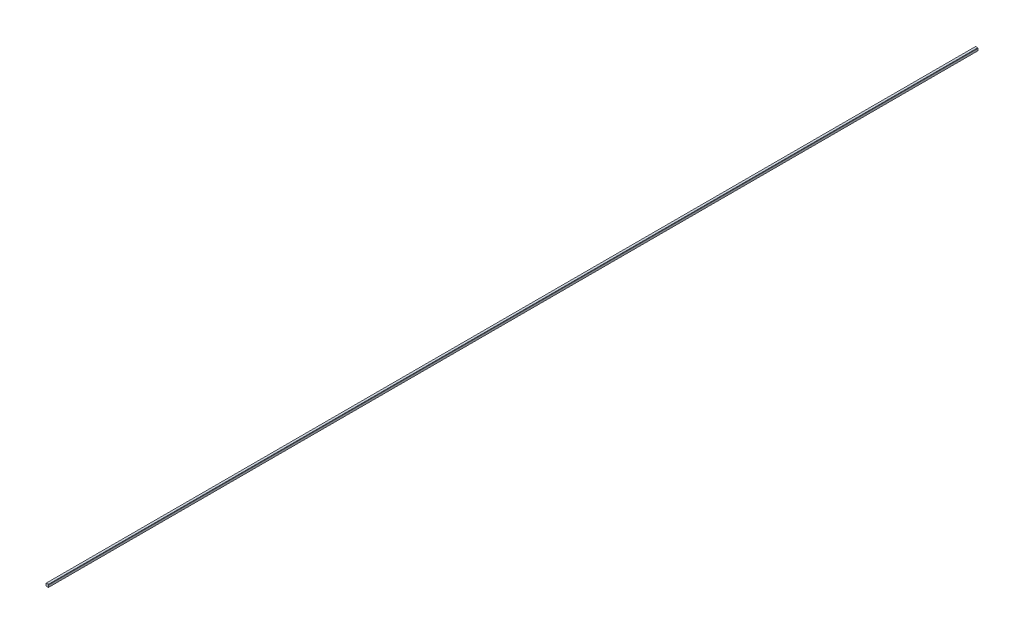
SolidWorks part; units mm, degrees
ref_plane "Front Plane" through (0, 0, 0) normal (0, 0, 1) x (1, 0, 0)
ref_plane "Top Plane" through (0, 0, 0) normal (0, 1, 0) x (1, 0, 0)
ref_plane "Right Plane" through (0, 0, 0) normal (1, 0, 0) x (0, 0, -1)
sketch "Sketch1" plane through (0, 0, 0) normal (0, 0, 1) x (1, 0, 0)
  line L0 (-0.2, 0.25) -> (-0.25, 0.2)
  line L1 (0.2, 0.25) -> (-0.2, 0.25)
  line L2 (0.25, 0.2) -> (0.25, -0.2)
  line L3 (0.2, -0.25) -> (-0.2, -0.25)
  line L4 (-0.25, 0.2) -> (-0.25, -0.2)
  line L5 (0.25, 0.25) -> (-0.25, -0.25) construction
  line L6 (0.25, -0.25) -> (-0.25, 0.25) construction
  line L7 (0.25, 0.2) -> (0.2, 0.25)
  line L8 (0.25, -0.2) -> (0.2, -0.25)
  line L9 (-0.2, -0.25) -> (-0.25, -0.2)
  point P0 (0, 0)
  dimension "D1" = 0.5
  dimension "D2" = 0.5
extrude "Boss-Extrude1" add sketch "Sketch1" along normal blind 170
